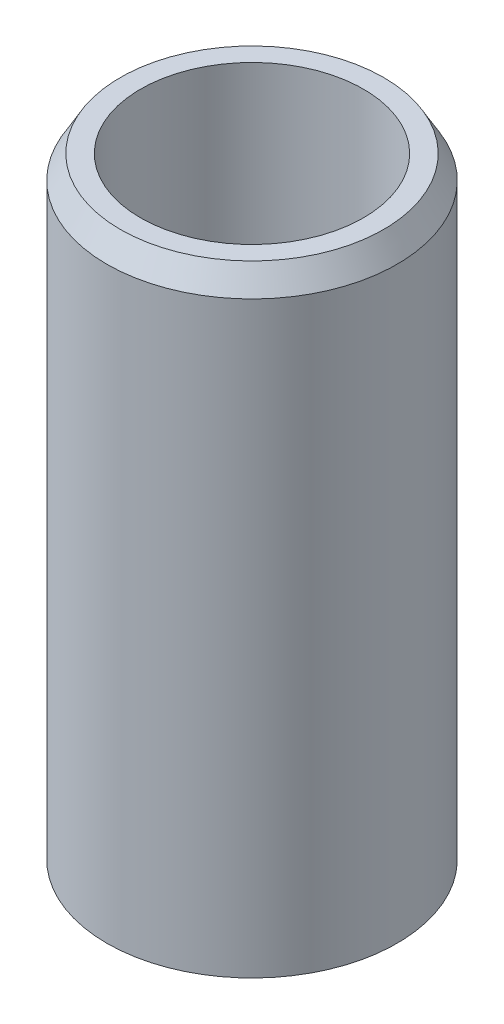
SolidWorks part; units mm, degrees
ref_plane "Front Plane" through (0, 0, 0) normal (0, 0, 1) x (1, 0, 0)
ref_plane "Top Plane" through (0, 0, 0) normal (0, 1, 0) x (1, 0, 0)
ref_plane "Right Plane" through (0, 0, 0) normal (1, 0, 0) x (0, 0, -1)
sketch "Sketch1" plane through (0, 0, 0) normal (0, 1, 0) x (1, 0, 0)
  circle A0 centre (0, 0) radius 32.5
  dimension "SHAFT_OD" = 65
extrude "Boss-Extrude1" add sketch "Sketch1" along normal blind 139.9207
sketch "Sketch2" plane through (0, 0, 0) normal (0, 1, 0) x (1, 0, 0)
  circle A0 centre (0, 0) radius 24.9664
  dimension "BORE_D" = 49.9327
extrude "Cut-Extrude1" cut sketch "Sketch2" along normal through all
chamfer "Chamfer1" distance 5.231 angle 30 2 edges at (0, 139.9207, 32.5) (0, 0, 32.5) first distance on face at (0, 139.9207, 32.5) first distance on face at (0, 0, 24.9664)
